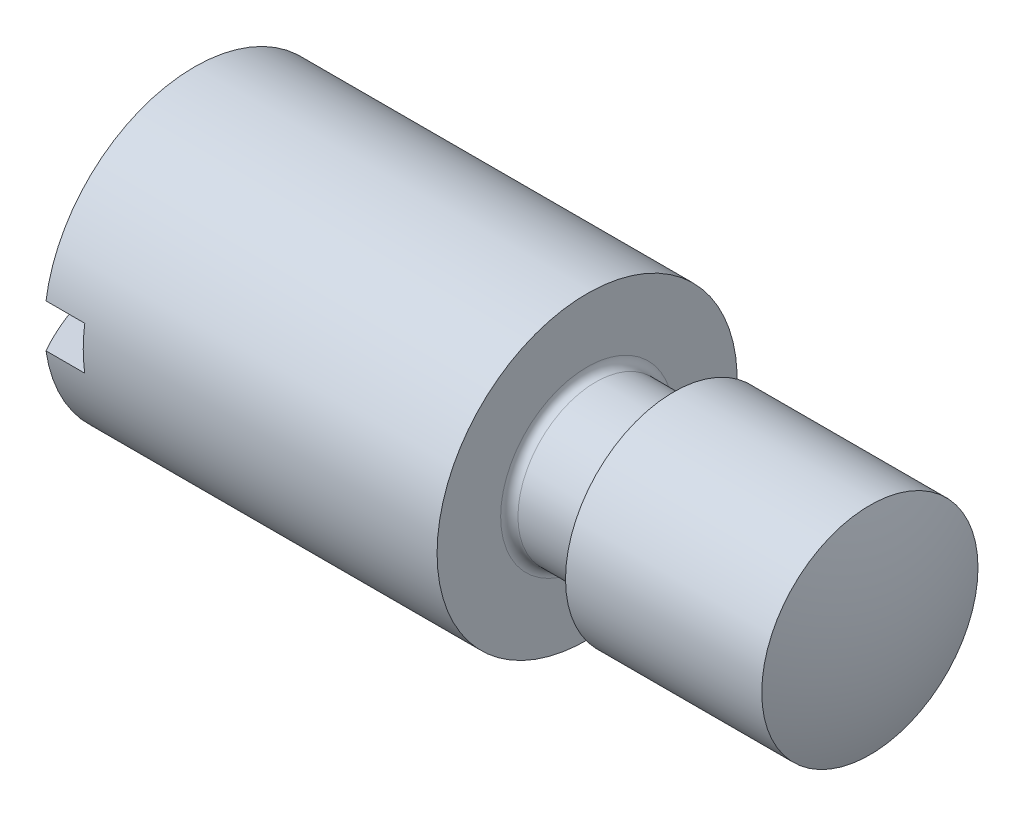
SolidWorks part; units mm, degrees
ref_plane "Front" through (0, 0, 0) normal (0, 0, 1) x (1, 0, 0)
ref_plane "Top" through (0, 0, 0) normal (0, 1, 0) x (1, 0, 0)
ref_plane "Right" through (0, 0, 0) normal (1, 0, 0) x (0, 0, -1)
sketch "Sketch1" plane through (9.9662, 0, 1.735) normal (0, 1, 0) x (1, 0, 0)
  line L0 (-1.4662, 1.735) -> (-9.9662, 1.735)
  line L1 (-3.9662, 2.985) -> (-3.9662, 2.635)
  line L2 (-1.6971, 2.985) -> (-3.9662, 2.985)
  line L3 (-4.9662, 2.635) -> (-4.9662, 3.47)
  line L4 (-4.9662, 3.47) -> (-9.5059, 3.47)
  line L5 (-14.465, 1.735) -> (1.5663, 1.735) construction
  line L6 (-3.9662, 2.635) -> (-4.9662, 2.635)
  arc A0 (-9.5059, 3.47) -> (-9.9662, 1.735) centre (-6.4662, 1.735) ccw
  arc A1 (-1.4662, 1.735) -> (-1.6971, 2.985) centre (-4.9662, 1.735) ccw
  dimension "l" = 5
  dimension "d" = 2.5
  dimension "b" = 3.5
revolve "Revolve1" add sketch "Sketch1" angle 360 about L5
cosmetic thread "ThreadCosmetic1" [suppressed] parameters "D2"=1.875
sketch "Sketch2" plane through (0, 0, 0) normal (0, 0, 1) x (1, 0, 0)
  line L0 (0.4603, 1.735) -> (0.4603, -1.735) construction
  line L1 (0.9089, 0.25) -> (0.0089, 0.25)
  line L2 (0.9089, 0.25) -> (0.9089, -0.25)
  line L3 (0.9089, -0.25) -> (0.0089, -0.25)
  arc A0 (0.0089, 0.25) -> (0.0089, -0.25) centre (0.0089, 0) ccw
  arc A1 (0.4603, 1.735) -> (0.4603, -1.735) centre (3.5, 0) ccw construction
  dimension "m" = 0.25
  dimension "t" = 0.4486
extrude "Cut-Extrude1" cut sketch "Sketch2" against normal through all and the other way through all
fillet "Fillet2" radius 0.1 2 edges at (6, 0, 0.9) (5, 0, 0.9)
sketch "Sketch3" plane through (0, 0, 0) normal (0, 1, 0) x (1, 0, 0)
  line L0 (8.2692, 0.9794) -> (8.4254, 1.25)
  line L1 (8.4254, 1.25) -> (8.4254, 1.5625)
  line L2 (8.4254, 1.5625) -> (8.1129, 1.5625)
  line L3 (8.1129, 1.5625) -> (8.1129, 1.25)
  line L4 (8.1129, 1.25) -> (8.2692, 0.9794)
  line L5 (8.2692, 1.25) -> (8.2692, -1.25) construction
  line L7 (0, 0) -> (10.589, 0) construction
  line L8 (8.2692, 1.25) -> (6, 1.25) construction
  dimension "D1" = 0.3125
revolve "Cut-Revolve10" [suppressed] cut sketch "Sketch3" angle 360 about L7
pattern_linear "LPattern10" [suppressed] count 7 spacing 0.375 along (-1, 0, 0) of bodies 103
equation "\"m@Sketch2\" = \"n@Sketch2\" / 2"
equation "\"D1@Sketch3\" =  ( \"d@Sketch1\" - \"D2@ThreadCosmetic1\" )  / 2"
equation "\"D3@LPattern10\" = \"D1@Sketch3\" * 1.2"
equation "\"D1@LPattern10\" =  ( \"b@Sketch1\" - \"a@Sketch1\" )  / \"D3@LPattern10\""
